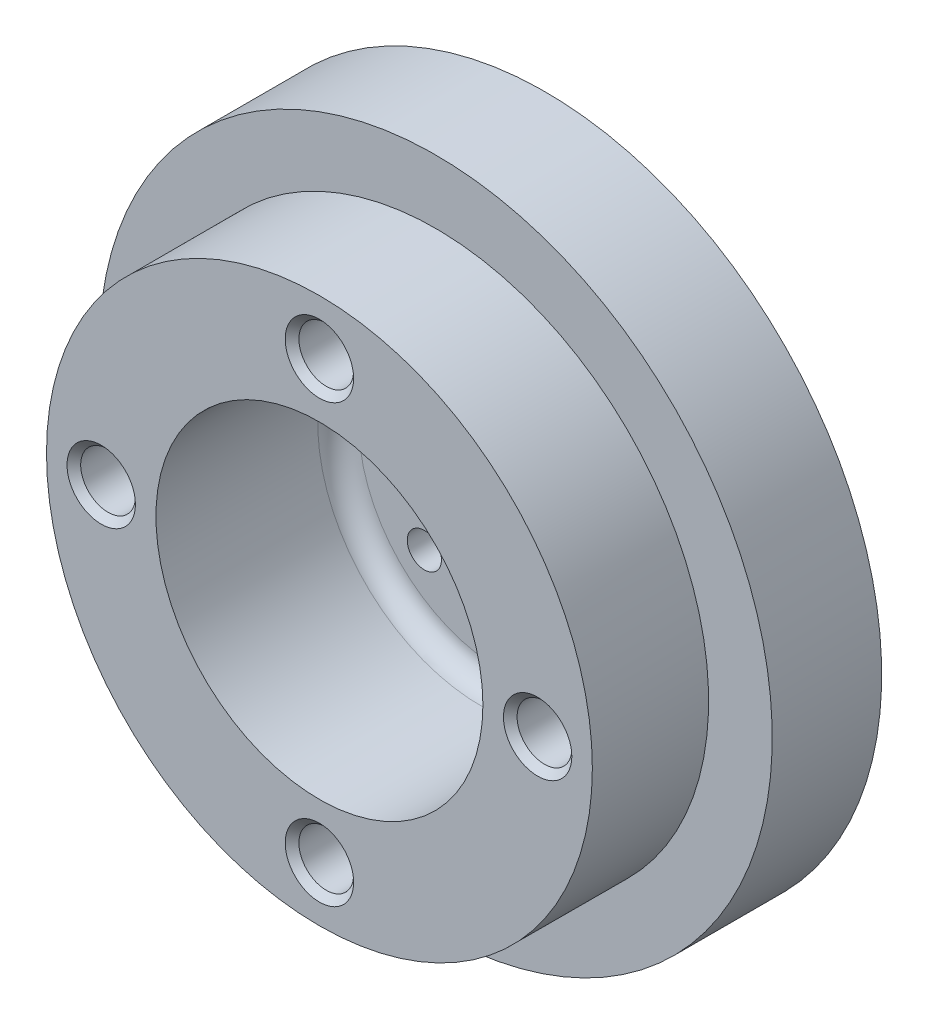
SolidWorks part; units mm, degrees
ref_plane "Front Plane" through (0, 0, 0) normal (0, 0, 1) x (1, 0, 0)
ref_plane "Top Plane" through (0, 0, 0) normal (0, 1, 0) x (1, 0, 0)
ref_plane "Right Plane" through (0, 0, 0) normal (1, 0, 0) x (0, 0, -1)
sketch "Sketch1" plane through (0, 0, 0) normal (0, 0, 1) x (1, 0, 0)
  circle A2 centre (0, 12) radius 4.2
  circle A3 centre (0, 12) radius 4.2
  circle A5 centre (0, 12) radius 19.75
  circle A6 centre (0, 12) radius 19.75
  circle A11 centre (5.6569, 17.6569) radius 1.25
  circle A12 centre (5.6569, 17.6569) radius 1.25
  circle A49 centre (8, 12) radius 1.25
  circle A50 centre (8, 12) radius 1.25
  circle A52 centre (5.6569, 6.3431) radius 1.25
  circle A53 centre (5.6569, 6.3431) radius 1.25
  circle A55 centre (0, 4) radius 1.25
  circle A56 centre (0, 4) radius 1.25
  circle A58 centre (-5.6569, 6.3431) radius 1.25
  circle A59 centre (-5.6569, 6.3431) radius 1.25
  circle A61 centre (-8, 12) radius 1.25
  circle A62 centre (-8, 12) radius 1.25
  circle A64 centre (-5.6569, 17.6569) radius 1.25
  circle A65 centre (-5.6569, 17.6569) radius 1.25
  circle A67 centre (0, 20) radius 1.25
  circle A68 centre (0, 20) radius 1.25
  dimension "D1" = 0.2
  dimension "D2" = 0.25
  dimension "D3" = 0.5
  dimension "D4" = 0.5
  dimension "D5" = 0.5
  dimension "D6" = 0.5
  dimension "D7" = 0.5
  dimension "D8" = 0.5
  dimension "D9" = 0.5
  dimension "D10" = 0.5
extrude "Boss-Extrude1" add sketch "Sketch1" along normal blind 3.175
sketch "Sketch3" plane through (0, 0, 3.175) normal (0, 0, 1) x (1, 0, 0)
  circle A1 centre (0, 12) radius 19.95
  circle A2 centre (0, 12) radius 11.95
  dimension "D2" = 39.9
  dimension "D1" = 8
extrude "Boss-Extrude2" add sketch "Sketch3" along normal offset from surface (13.325 mm away) 0.5
sketch "Sketch4" plane through (0, 0, 16.5) normal (0, 0, 1) x (1, 0, 0)
  line L0 (-19.95, 12) -> (-11.95, 12) construction
  circle A0 centre (-15.95, 12) radius 2
  circle A1 centre (0, 12) radius 19.95 construction
  circle A2 centre (0, 12) radius 11.95 construction
  point P9 (-15.95, 12)
  dimension "D1" = 4
extrude "Cut-Extrude1" cut sketch "Sketch4" against normal through all
pattern_circular "CirPattern1" count 4 over 360 about axis through (0, 12, 73.4271) along (0, 0, -1) of "Cut-Extrude1" reverse direction yes
sketch "Sketch5" plane through (0, 0, 0) normal (0, 0, -1) x (-1, 0, 0)
  circle A0 centre (0, 12) radius 19.75 construction
  circle A1 centre (0, 12) radius 19.75
  circle A2 centre (0, 12) radius 24.6 construction
  circle A3 centre (0, 12) radius 24.6
extrude "Boss-Extrude3" add sketch "Sketch5" against normal up to surface (8 mm away)
chamfer "Chamfer1" distance 0.5 angle 45 4 edges at (13.95, 12, 16.5) (0, 25.95, 16.5) (0, -1.95, 16.5) (-13.95, 12, 16.5)
fillet "Fillet1" radius 1.5 1 edges at (11.95, 12, 3.175)
equation "\"D9@Sketch1\"=\"D10@Sketch1\""
equation "\"D8@Sketch1\"=\"D10@Sketch1\""
equation "\"D7@Sketch1\"=\"D10@Sketch1\""
equation "\"D6@Sketch1\"=\"D10@Sketch1\""
equation "\"D5@Sketch1\"=\"D10@Sketch1\""
equation "\"D4@Sketch1\"=\"D10@Sketch1\""
equation "\"D3@Sketch1\"=\"D10@Sketch1\""
